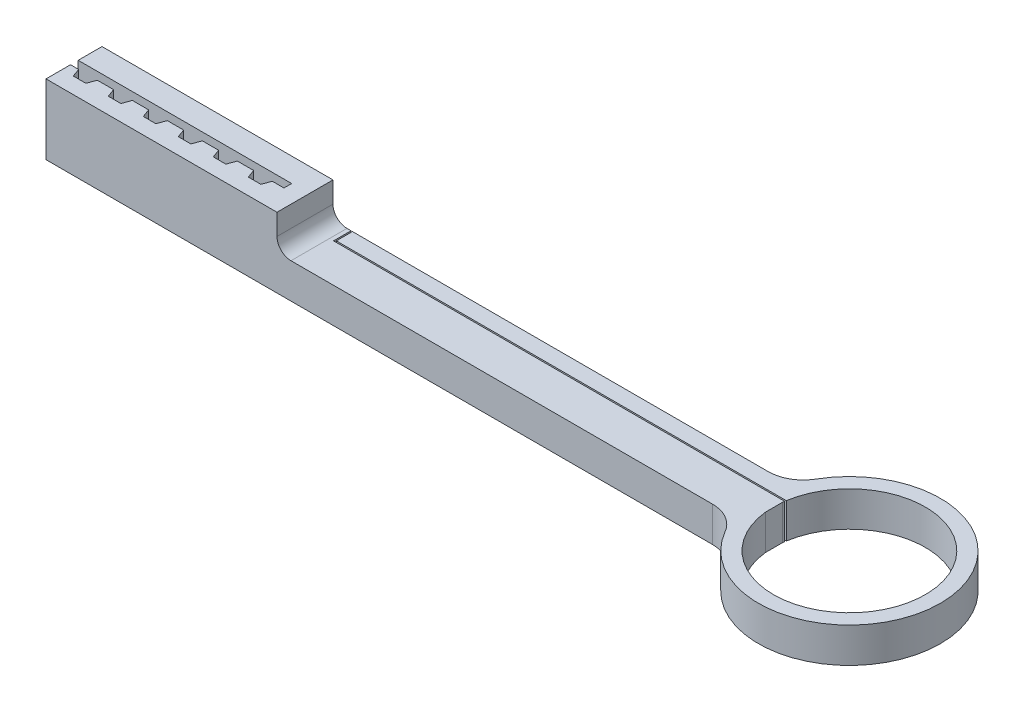
SolidWorks part; units mm, degrees
ref_plane "Спереди" through (0, 0, 0) normal (0, 0, 1) x (1, 0, 0)
ref_plane "Сверху" through (0, 0, 0) normal (0, 1, 0) x (1, 0, 0)
ref_plane "Справа" through (0, 0, 0) normal (1, 0, 0) x (0, 0, -1)
sketch "Эскиз1" plane through (0, 0, 0) normal (0, 1, 0) x (1, 0, 0)
  circle A0 centre (0, 0) radius 10.85
  circle A1 centre (0, 0) radius 13
  dimension "D1" = 21.7
  dimension "D2" = 26
extrude "ring" add sketch "Эскиз1" along normal blind 5
sketch "Эскиз2" plane through (0, 0, 0) normal (0, 1, 0) x (1, 0, 0)
  line L0 (34.0214, 0) -> (-42.1067, 0) construction
  line L2 (-10.7819, 4) -> (-110.7819, 4)
  line L3 (-10.7819, 4) -> (-10.7819, -4)
  line L4 (-10.7819, -4) -> (-110.7819, -4)
  line L5 (-110.7819, 4) -> (-110.7819, -4)
  circle A0 centre (0, 0) radius 11.5 construction
  point P9 (-10.7819, 0)
  dimension "D3" = 23
  dimension "D2" = 8
  dimension "D4" = 100
extrude "stick" add sketch "Эскиз2" along normal blind 5
sketch "Эскиз3" plane through (0, 0, 0) normal (0, 1, 0) x (1, 0, 0)
  line L0 (-110.7819, -4) -> (-12.3693, -4) construction
  line L1 (-110.7819, 4) -> (-77.7819, 4)
  line L2 (-110.7819, 4) -> (-110.7819, -4)
  line L3 (-110.7819, -4) -> (-77.7819, -4)
  line L4 (-77.7819, 4) -> (-77.7819, -4)
  dimension "D1" = 33
extrude "key" add sketch "Эскиз3" along normal blind 10
fillet "Скругление1" radius 5 2 edges at (-12.3693, 2.5, 4) (-12.3693, 2.5, -4)
ref_plane "Плоскость1" through (0, 2.5, 0) normal (0, 1, 0) x (-1, 0, 0)
sketch "Эскиз4" plane through (0, 2.5, 0) normal (0, 1, 0) x (1, 0, 0)
  line L0 (-110.7819, 0) -> (-77.7819, 0) construction
  line L1 (-110.7819, 4) -> (-110.7819, -4) construction
  line L2 (-77.7819, -4) -> (-77.7819, 4) construction
  line L3 (-110.7819, 0.6) -> (-80.2819, 0.6)
  line L4 (-109.1819, -1.7) -> (-107.3819, -1.7)
  line L5 (-109.6187, -0.5) -> (-90.7763, -0.5) construction
  line L6 (-109.6187, -0.5) -> (-109.1819, -1.7) construction
  line L7 (-109.6187, -0.5) -> (-109.1819, -1.7)
  line L8 (-107.3819, -1.7) -> (-106.9452, -0.5)
  line L9 (-108.2819, 1.0157) -> (-108.2819, -3.4603) construction
  line L10 (-109.6187, -0.5) -> (-110.7819, -0.5)
  line L11 (-106.9452, -0.5) -> (-105.7819, -0.5)
  line L12 (-110.7819, 0.6) -> (-110.7819, -0.5)
  line L13 (-104.6187, -0.5) -> (-105.7819, -0.5)
  line L14 (-104.1819, -1.7) -> (-102.3819, -1.7)
  line L15 (-102.3819, -1.7) -> (-101.9452, -0.5)
  line L16 (-101.9452, -0.5) -> (-100.7819, -0.5)
  line L17 (-104.6187, -0.5) -> (-104.1819, -1.7)
  line L18 (-99.6187, -0.5) -> (-100.7819, -0.5)
  line L19 (-99.1819, -1.7) -> (-97.3819, -1.7)
  line L20 (-97.3819, -1.7) -> (-96.9452, -0.5)
  line L21 (-96.9452, -0.5) -> (-95.7819, -0.5)
  line L22 (-99.6187, -0.5) -> (-99.1819, -1.7)
  line L24 (-94.6187, -0.5) -> (-95.7819, -0.5)
  line L25 (-94.1819, -1.7) -> (-92.3819, -1.7)
  line L26 (-92.3819, -1.7) -> (-91.9452, -0.5)
  line L27 (-91.9452, -0.5) -> (-90.7819, -0.5)
  line L28 (-94.6187, -0.5) -> (-94.1819, -1.7)
  line L43 (-89.6187, -0.5) -> (-90.7819, -0.5)
  line L44 (-89.1819, -1.7) -> (-87.3819, -1.7)
  line L45 (-87.3819, -1.7) -> (-86.9452, -0.5)
  line L46 (-86.9452, -0.5) -> (-85.7819, -0.5)
  line L47 (-89.6187, -0.5) -> (-89.1819, -1.7)
  line L48 (-84.6187, -0.5) -> (-85.7819, -0.5)
  line L49 (-84.1819, -1.7) -> (-82.3819, -1.7)
  line L50 (-82.3819, -1.7) -> (-81.9452, -0.5)
  line L51 (-81.9452, -0.5) -> (-80.7819, -0.5)
  line L52 (-84.6187, -0.5) -> (-84.1819, -1.7)
  line L53 (-80.7819, -0.5) -> (-80.2819, -0.5)
  line L54 (-80.2819, 0.6) -> (-80.2819, -0.5)
  point P12 (-108.2819, -1.7)
  dimension "D1" = 1.8
  dimension "D2" = 0.6
  dimension "D3" = 0.5
  dimension "D4" = 1.2
  dimension "D5" = 110
  dimension "D6" = 5
  dimension "D7" = 40
  dimension "D8" = 0.5
fillet "Скругление5" radius 2 1 edges at (-77.7819, 5, 0)
extrude "key hole" cut sketch "Эскиз4" against normal through all and the other way through all
sketch "Эскиз5" plane through (0, 0, 0) normal (0, -1, 0) x (1, 0, 0)
  line L0 (0, 0) -> (-70.3859, 0) construction
  line L1 (-75.2, -4) -> (-75.2, -1.5)
  line L3 (-75.2, -1.5) -> (0, -1.5)
  line L4 (0, -1.5) -> (0, -1.7)
  line L5 (0, -1.7) -> (-75, -1.7)
  line L6 (-75, -1.7) -> (-75, -4)
  line L7 (-75, -4) -> (-75.2, -4)
  line L8 (-15.5885, -4) -> (-110.7819, -4) construction
  dimension "D1" = 0.2
  dimension "D2" = 0.2
  dimension "D3" = 75
  dimension "D4" = 1.5
extrude "Вытянуть2" cut sketch "Эскиз5" against normal through all
